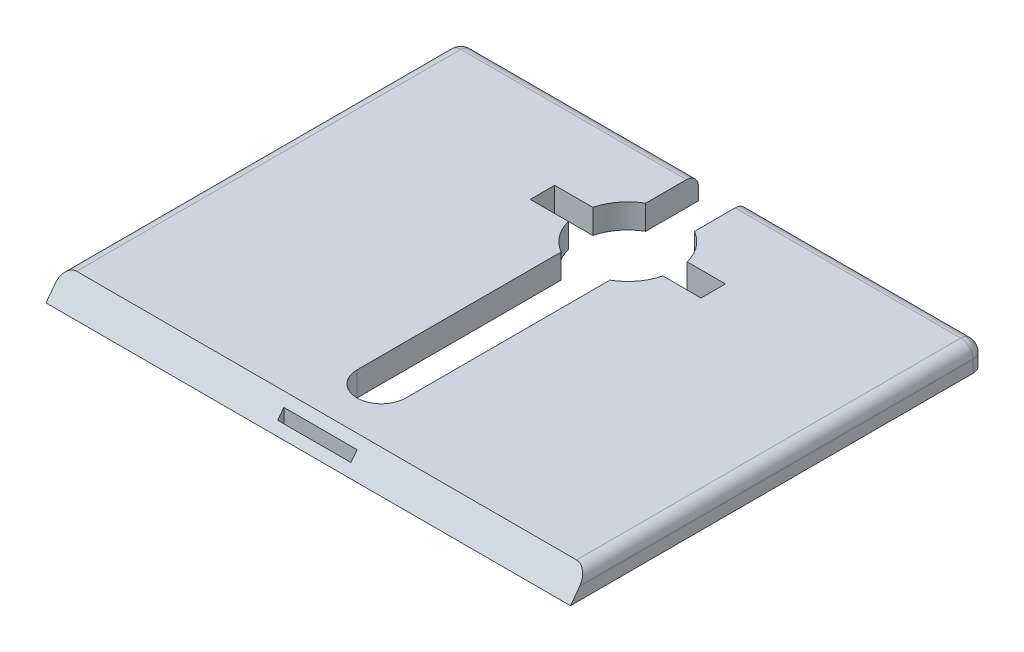
SolidWorks part; units mm, degrees
ref_plane "Ebene vorne" through (0, 0, 0) normal (0, 0, 1) x (1, 0, 0)
ref_plane "Ebene oben" through (0, 0, 0) normal (0, 1, 0) x (1, 0, 0)
ref_plane "Ebene rechts" through (0, 0, 0) normal (1, 0, 0) x (0, 0, -1)
sketch "Skizze1" plane through (0, 0, 0) normal (0, 1, 0) x (1, 0, 0)
  line L1 (-10.75, -8.5) -> (10.75, -8.5)
  line L2 (-10.75, -8.5) -> (-10.75, 8.5)
  line L3 (-10.75, 8.5) -> (10.75, 8.5)
  line L4 (10.75, -8.5) -> (10.75, 8.5)
  line L5 (-10.75, -8.5) -> (10.75, 8.5) construction
  line L6 (-10.75, 8.5) -> (10.75, -8.5) construction
  point P0 (0, 0)
  dimension "D1" = 17
  dimension "D2" = 21.5
extrude "Aufsatz-Linear austragen1" add sketch "Skizze1" along normal blind 1
fillet "Verrundung1" radius 0.5 3 edges at (10.75, 1, 0) (0, 1, -8.5) (-10.75, 1, 0)
sketch "Skizze2" plane through (-10.75, 0, 0) normal (-1, 0, 0) x (0, 0, 1)
  line L0 (8.5, 0) -> (7.75, 1)
  line L1 (-8, 1) -> (8.5, 1) construction
  line L2 (7.75, 1) -> (8.5, 1)
  line L3 (8.5, 1) -> (8.5, 0)
  dimension "D1" = 0.75
extrude "Schnitt-Linear austragen1" cut sketch "Skizze2" against normal up to surface (21.5 mm away) up to face at (10.75, 0.25, 0)
sketch "Skizze4" plane through (0, 1, 0) normal (0, 1, 0) x (1, 0, 0)
  line L6 (10.25, -7.75) -> (-10.25, -7.75) construction
  line L7 (-1.5, -8.25) -> (1.5, -8.25)
  line L8 (-1.5, -8.25) -> (-1.5, -8)
  line L9 (-1.5, -8) -> (1.5, -8)
  line L10 (1.5, -8.25) -> (1.5, -8)
  line L11 (-1.5, -8.25) -> (1.5, -8) construction
  line L12 (-1.5, -8) -> (1.5, -8.25) construction
  line L13 (-10.75, -8.125) -> (-10.75, -8.5) construction
  point P0 (0, -8.125)
  dimension "D1" = 0.25
  dimension "D2" = 0.25
  dimension "D3" = 3
  dimension "D4" = 10.75
extrude "Schnitt-Linear austragen2" cut sketch "Skizze4" against normal up to surface (1 mm away) up to face at (0, 0, 0)
fillet "Verrundung2" radius 0.5 4 edges at (10.6036, 0.8536, -8.3536) (-10.6036, 0.8536, -8.3536) (10.75, 0.25, -8.5) (-10.75, 0.25, -8.5)
sketch "Skizze5" plane through (0, 1, 0) normal (0, 1, 0) x (1, 0, 0)
  line L0 (-10.75, 8) -> (-10.75, -8.5) construction
  line L1 (-3.5, 4.1) -> (3.5, 4.1)
  line L2 (-3.5, 4.1) -> (-3.5, 5.1)
  line L3 (-3.5, 5.1) -> (3.5, 5.1)
  line L4 (3.5, 4.1) -> (3.5, 5.1)
  line L5 (-3.5, 4.1) -> (3.5, 5.1) construction
  line L6 (-3.5, 5.1) -> (3.5, 4.1) construction
  line L7 (-10.25, 8.5) -> (10.25, 8.5) construction
  circle A0 centre (0, 4.6) radius 2
  dimension "D2" = 4
  dimension "D1" = 7
  dimension "D3" = 1
  dimension "D4" = 10.75
  dimension "D5" = 3.9
extrude "Schnitt-Linear austragen3" cut sketch "Skizze5" against normal up to surface (1 mm away) contours A0 L3 L2 L1 | L3 A0 | L1 A0 L3 | L1 A0 | A0 L1 L4 L3 region at (-2.7394, 1, -4.6) region at (0, 1, -4.6) region at (0, 1, -3.4752) region at (2.7394, 1, -4.6) region at (0, 1, -5.7248) up to face at (0, 0, 8.125)
sketch "Skizze6" plane through (0, 1, 0) normal (0, 1, 0) x (1, 0, 0)
  line L0 (0, 8.5) -> (0, -5.5) construction
  line L1 (-10.25, 8.5) -> (10.25, 8.5) construction
  line L2 (1, 8.5) -> (1, -5.5)
  line L3 (-1, 8.5) -> (-1, -5.5)
  line L5 (10.25, -7.75) -> (10.25, 8) construction
  arc A0 (1, 8.5) -> (-1, 8.5) centre (0, 8.5) ccw
  arc A1 (-1, -5.5) -> (1, -5.5) centre (0, -5.5) ccw
  point P4 (0, 1.5)
  dimension "D3" = 14
  dimension "D1" = 10.25
  dimension "D2" = 1
extrude "Schnitt-Linear austragen4" cut sketch "Skizze6" against normal up to surface (1 mm away) up to face at (0, 0, -4.6)
